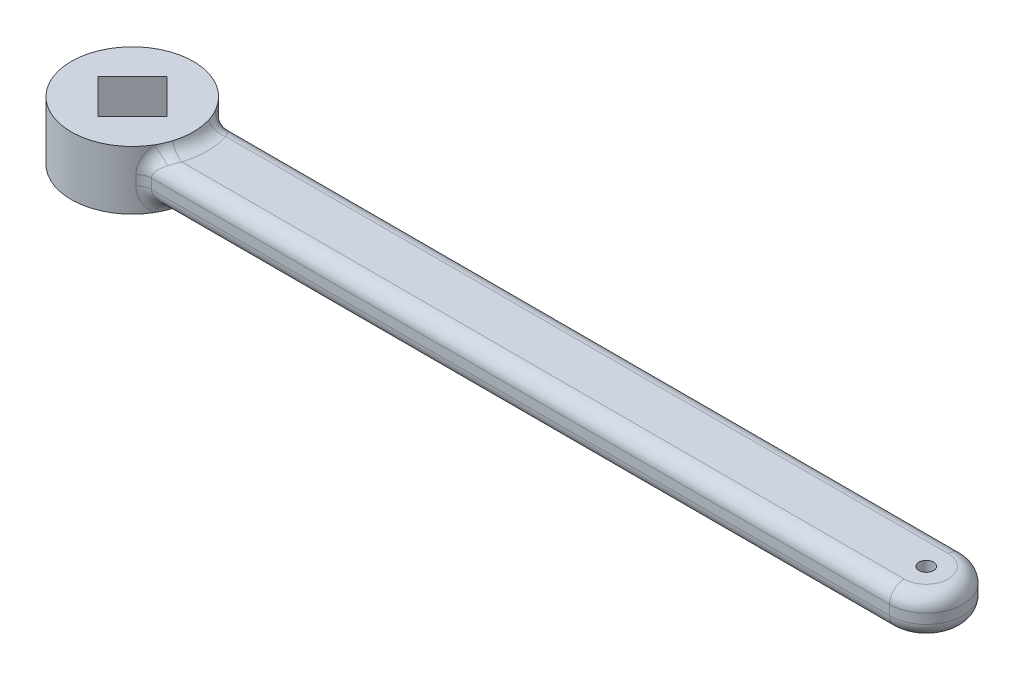
SolidWorks part; units mm, degrees
ref_plane "Спереди" through (0, 0, 0) normal (0, 0, 1) x (1, 0, 0)
ref_plane "Сверху" through (0, 0, 0) normal (0, 1, 0) x (1, 0, 0)
ref_plane "Справа" through (0, 0, 0) normal (1, 0, 0) x (0, 0, -1)
sketch "Эскиз1" plane through (0, 0, 0) normal (0, 1, 0) x (1, 0, 0)
  circle A0 centre (0, 0) radius 12.5
  dimension "D1" = 25
extrude "Бобышка-Вытянуть1" add sketch "Эскиз1" along normal mid plane 12
sketch "Эскиз2" plane through (0, 0, 0) normal (0, 1, 0) x (1, 0, 0)
  line L0 (0, 0) -> (162.5, 0) construction
  line L1 (0, 7.5) -> (162.5, 7.5)
  line L2 (0, -7.5) -> (162.5, -7.5)
  arc A0 (0, 7.5) -> (0, -7.5) centre (0, 0) ccw
  arc A1 (162.5, -7.5) -> (162.5, 7.5) centre (162.5, 0) ccw
  circle A2 centre (162.5, 0) radius 1.5
  point P3 (81.25, 0)
  dimension "D3" = 3
  dimension "D1" = 15
  dimension "D2" = 162.5
extrude "Бобышка-Вытянуть2" add sketch "Эскиз2" along normal mid plane 8
sketch "Эскиз3" plane through (0, 6, 0) normal (0, 1, 0) x (1, 0, 0)
  line L0 (-7.0711, 0) -> (0, 7.0711)
  line L1 (-7.0711, 0) -> (0, -7.0711)
  line L2 (0, 7.0711) -> (7.0711, 0)
  line L3 (0, -7.0711) -> (7.0711, 0)
  line L4 (-7.0711, 0) -> (7.0711, 0) construction
  line L5 (0, 7.0711) -> (0, -7.0711) construction
  point P1 (0, 0)
  dimension "D1" = 10
extrude "Вырез-Вытянуть1" cut sketch "Эскиз3" against normal through all
fillet "Скругление4" radius 3 6 edges at (86.25, -4, -7.5) (170, -4, 0) (86.25, 4, -7.5) (170, 4, 0) (86.25, -4, 7.5) (86.25, 4, 7.5)
fillet "Скругление5" radius 3 6 edges at (10.3421, 2.6266, 7.0207) (10, 0, 7.5) (10.6881, -3.2522, 6.4818) (10.3421, -2.6266, -7.0207) (10, 0, -7.5) (10.6881, 3.2522, -6.4818)
